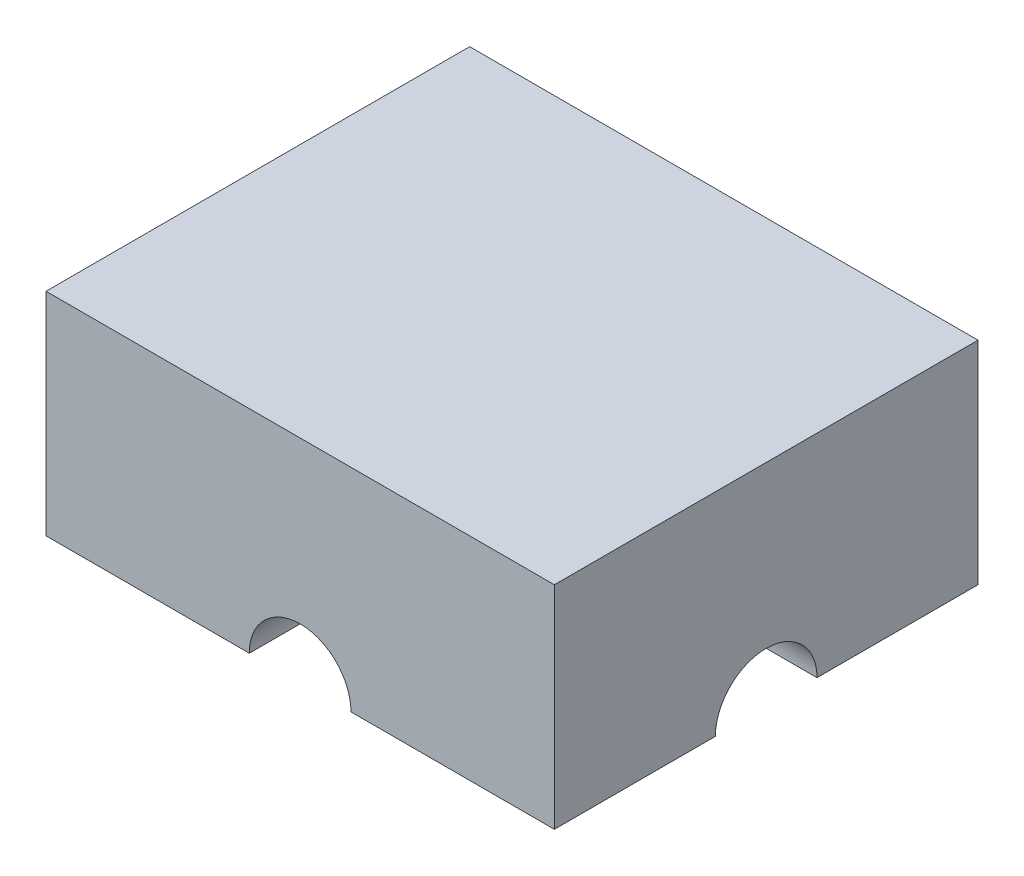
SolidWorks part; units mm, degrees
ref_plane "Front Plane" through (0, 0, 0) normal (0, 0, 1) x (1, 0, 0)
ref_plane "Top Plane" through (0, 0, 0) normal (0, 1, 0) x (1, 0, 0)
ref_plane "Right Plane" through (0, 0, 0) normal (1, 0, 0) x (0, 0, -1)
sketch "Sketch1" plane through (0, 0, 0) normal (0, 0, 1) x (1, 0, 0)
  line L1 (-60, 0) -> (60, 0)
  line L2 (-60, 0) -> (-60, 50)
  line L3 (-60, 50) -> (60, 50)
  line L4 (60, 0) -> (60, 50)
  point P4 (0, 0)
  dimension "D1" = 120
  dimension "D2" = 50
extrude "Boss-Extrude1" add sketch "Sketch1" against normal blind 100
sketch "Sketch2" plane through (0, 0, 0) normal (0, 0, 1) x (1, 0, 0)
  circle A0 centre (0, 0) radius 12
  dimension "D1" = 24
extrude "Cut-Extrude1" cut sketch "Sketch2" against normal blind 50
sketch "Sketch3" plane through (-60, 0, 0) normal (-1, 0, 0) x (0, 0, 1)
  circle A0 centre (-50, 0) radius 12
  dimension "D1" = 24
extrude "Cut-Extrude2" cut sketch "Sketch3" against normal through all
fillet "Fillet1" radius 3 2 edges at (8.4853, 8.4853, -41.5147) (-8.4853, 8.4853, -41.5147)
